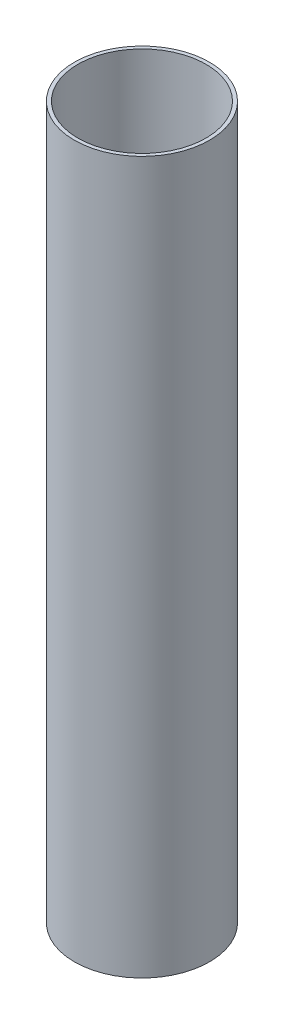
SolidWorks part; units mm, degrees
ref_plane "Front Plane" through (0, 0, 0) normal (0, 0, 1) x (1, 0, 0)
ref_plane "Top Plane" through (0, 0, 0) normal (0, 1, 0) x (1, 0, 0)
ref_plane "Right Plane" through (0, 0, 0) normal (1, 0, 0) x (0, 0, -1)
sketch "Sketch2" plane through (0, 0, 0) normal (0, 1, 0) x (1, 0, 0)
  circle A0 centre (0, 0) radius 36
  circle A1 centre (0, 0) radius 38
  dimension "D1" = 2
  dimension "D2" = 76
extrude "Boss-Extrude1" add sketch "Sketch2" along normal blind 400
ref_axis "Axis1" through (41.8, 0, 0) along (-1, 0, 0)
ref_plane "Plane1" through (0, 0, 0) normal (0, 0.2045, 0.9789) x (-1, 0, 0)
sketch "Sketch3" plane through (0, 0, 0) normal (0, 0.2045, 0.9789) x (-1, 0, 0)
  line L0 (0, 41.8) -> (0, -41.8) construction
  line L2 (-41.8, 0) -> (41.8, 0) construction
  arc A0 (8.5, -185) -> (-8.5, -185) centre (0, -185) ccw
  arc A1 (-8.5, -185) -> (8.5, -185) centre (0, -185) ccw construction
  ellipse E0 centre (0, -185) end of major axis (0, -202) minor radius 8.5 (-8.5, -185) -> (8.5, -185) ccw
  dimension "D1" = 17
  dimension "D2" = 185
  dimension "D3" = 17
extrude "Cut-Extrude1" cut sketch "Sketch3" along normal up to next and the other way up to next
